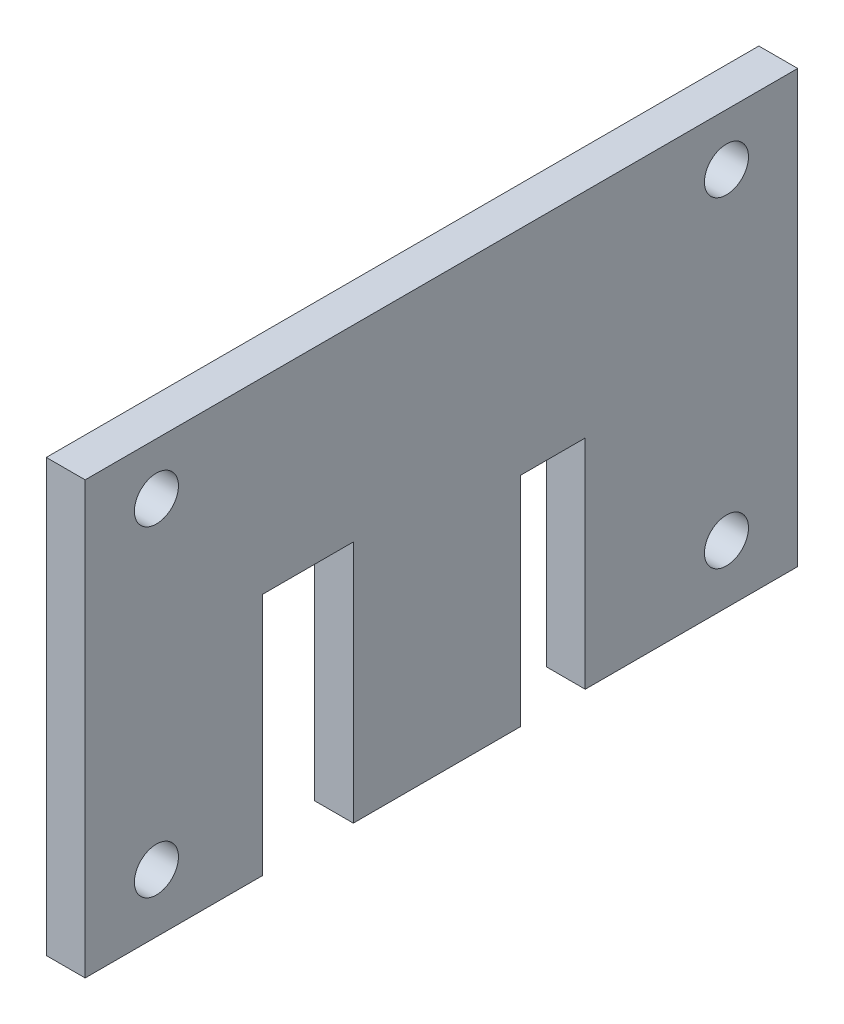
SolidWorks part; units mm, degrees
ref_plane "Front Plane" through (0, 0, 0) normal (0, 0, 1) x (1, 0, 0)
ref_plane "Top Plane" through (0, 0, 0) normal (0, 1, 0) x (1, 0, 0)
ref_plane "Right Plane" through (0, 0, 0) normal (1, 0, 0) x (0, 0, -1)
ref_plane "PX72_4" through (72.4, 0, 0) normal (1, 0, 0) x (0, 0, -1)
sketch "Sketch1" plane through (72.4, 0, 0) normal (1, 0, 0) x (0, 0, -1)
  line L0 (-99.5, -26.8) -> (-44.5, -26.8)
  line L1 (-44.5, -26.8) -> (-44.5, 6.5)
  line L2 (-44.5, 6.5) -> (-99.5, 6.5)
  line L3 (-99.5, 6.5) -> (-99.5, -26.8)
extrude "Cover Plate" add sketch "Sketch1" along normal blind 3
ref_plane "PX71_4" through (71.4, 0, 0) normal (1, 0, 0) x (0, 0, -1)
sketch "Sketch2" plane through (71.4, 0, 0) normal (1, 0, 0) x (0, 0, -1)
  line L0 (-85.8, -27.8) -> (-78.8, -27.8)
  line L1 (-78.8, -27.8) -> (-78.8, -8)
  line L2 (-78.8, -8) -> (-85.8, -8)
  line L3 (-85.8, -8) -> (-85.8, -27.8)
  line L4 (-65.9, -27.8) -> (-60.9, -27.8)
  line L5 (-60.9, -27.8) -> (-60.9, -10)
  line L6 (-60.9, -10) -> (-65.9, -10)
  line L7 (-65.9, -10) -> (-65.9, -27.8)
extrude "Cable Notches" cut sketch "Sketch2" along normal blind 5
sketch "Sketch3" plane through (71.4, 0, 0) normal (1, 0, 0) x (0, 0, -1)
  circle A0 centre (-94, -22.3) radius 1.7
  circle A1 centre (-94, 2.5) radius 1.7
  circle A2 centre (-50, -22.3) radius 1.7
  circle A3 centre (-50, 2.5) radius 1.7
extrude "Screw Holes" cut sketch "Sketch3" along normal blind 5
equation "\"BOARD_REAR\" = 86.0"
equation "\"BOARD_FRONT\" = 41.0"
equation "\"BOARD_END\" = 22.0"
equation "\"BOARD_ANGLED\" = 30.0"
equation "\"BOARD_DEPTH\" = 41.8431"
equation "\"PCB_T\" = 1.6"
equation "\"ABOVE_PCB\" = 14.0"
equation "\"BELOW_PCB\" = 6.0"
equation "\"MID_PARTS_H\" = 9.0"
equation "\"BOARD_HOLE_PILOT\" = 1.6"
equation "\"J2_X\" = 19.0"
equation "\"DUPONT_DROP\" = 14.0"
equation "\"BEND_R\" = 5.0"
equation "\"BOARD_GAP\" = 3.0"
equation "\"TOF_FOV\" = 25.0"
equation "\"TOF_MARGIN_DEG\" = 5.0"
equation "\"TOF_WIN_MARGIN\" = 1.0"
equation "\"TOF_Z\" = 9.0"
equation "\"TOF_SIDE_BEARING\" = 90.0"
equation "\"TOF_CONE_LEN\" = 70.0"
equation "\"CAM_W\" = 29.2"
equation "\"CAM_H\" = 28.2"
equation "\"CAM_D\" = 12.35"
equation "\"CAM_FRONT_Y\" = 43.0"
equation "\"CAM_BOTTOM_Z\" = 17.0"
equation "\"CAM_LENS_UP\" = 11.6"
equation "\"CAM_LENS_OPEN\" = 9.6"
equation "\"CAM_HFOV\" = 53.5"
equation "\"CAM_VFOV\" = 41.41"
equation "\"CAM_FOV_MARGIN\" = 3.0"
equation "\"CAM_FIT\" = 0.3"
equation "\"RIBBON_W\" = 16.0"
equation "\"RIBBON_T\" = 0.3"
equation "\"RIBBON_LEN\" = 150.0"
equation "\"RIBBON_EXIT_Y\" = 35.0"
equation "\"WALL\" = 2.4"
equation "\"HEAD_X\" = 48.4"
equation "\"HEAD_REAR_Y\" = -11.9"
equation "\"CAM_FOAM\" = 2.8"
equation "\"HEAD_FRONT_Y\" = 48.2"
equation "\"HEAD_TOP_Z\" = 50.6"
equation "\"HEAD_BOT_Z\" = -28.4"
equation "\"HEAD_SPLIT_Z\" = -4.0"
equation "\"SKIRT_T\" = 1.2"
equation "\"SKIRT_H\" = 3.0"
equation "\"SKIRT_FIT\" = 0.3"
equation "\"VISOR\" = 7.8"
equation "\"VISOR_Z\" = 40.0"
equation "\"ROOF_SLOPE_Y\" = 40.0"
equation "\"ROOF_CHAMFER\" = 10.0"
equation "\"REAR_CHAMFER\" = 10.0"
equation "\"CORNER_CHAMFER\" = 6.0"
equation "\"LOWER_SIDE_FACET\" = 6.0"
equation "\"LIGHTBAR_DEPTH\" = 1.0"
equation "\"HOOD_Z\" = 14.0"
equation "\"HOOD_L\" = 6.0"
equation "\"SIDE_HOOD_L\" = 4.0"
equation "\"INSERT_M3_D\" = 4.0"
equation "\"INSERT_M3_L\" = 6.0"
equation "\"M3_CLEAR\" = 3.4"
equation "\"M2_PILOT\" = 1.6"
equation "\"M25_PILOT\" = 2.2"
equation "\"BOX_X\" = 72.4"
equation "\"BOX_FRONT_Y\" = -11.9"
equation "\"BOX_REAR_Y\" = -124.4"
equation "\"BOX_BOT_Z\" = -28.4"
equation "\"BOX_TOP_Z\" = 28.0"
equation "\"LID_T\" = 2.4"
equation "\"LID_SKIRT\" = 1.6"
equation "\"LID_TONGUE_H\" = 3.0"
equation "\"LID_FIT\" = 0.3"
equation "\"PI_STANDOFF\" = 10.0"
equation "\"BOX_REAR_CHAMFER\" = 8.0"
equation "\"BOX_REAR_FACET\" = 4.0"
equation "\"VENT_UPSTAND\" = 3.0"
equation "\"TUBE_D\" = 22.2"
equation "\"TUBE_LINER\" = 1.0"
equation "\"MOUNT_Y\" = -70.0"
equation "\"RAIL_W\" = 30.0"
equation "\"RAIL_W2\" = 38.0"
equation "\"RAIL_H\" = 6.0"
equation "\"SLIDE\" = 0.3"
equation "\"STOP_T\" = 6.0"
equation "\"CLAMP_W\" = 40.0"
equation "\"CLAMP_HALF\" = 20.0"
equation "\"CLAMP_DROP\" = 12.0"
equation "\"CAP_T\" = 12.0"
equation "\"CLAMP_BOLT_OFF\" = 16.6"
equation "\"M5_INSERT_D\" = 6.4"
equation "\"M5_CLEAR\" = 5.5"
equation "\"LOCK_D\" = 3.3"
equation "\"POD_TILT_DEG\" = 0.0"
equation "\"PRINT_LIMIT\" = 180.0"
equation "\"PI5_L\" = 85.0"
equation "\"PI5_W\" = 56.0"
equation "\"PI5_T\" = 1.6"
equation "\"PI5_USBC_BX\" = 11.2"
equation "\"PI5_ETH_BY\" = 10.2"
equation "\"PI5_PORT_OVERHANG\" = 3.0"
equation "\"PI5_FPC_H\" = 5.0"
equation "\"PI5_FPC_USE\" = 0.0"
equation "\"PI5_PIN1_BX\" = 8.37"
equation "\"HEADER_BASE_H\" = 2.5"
equation "\"DUPONT_L\" = 14.0"
equation "\"PI5_UNDERSIDE\" = 1.5"
equation "\"COOLER_H\" = 15.0"
equation "\"HAT_W\" = 65.0"
equation "\"HAT_D\" = 56.5"
equation "\"HAT_T\" = 1.6"
equation "\"HAT_SPACER\" = 16.0"
equation "\"HAILO_H\" = 10.0"
equation "\"STACK_PINS_H\" = 6.0"
equation "\"DUPONT_SEAT\" = 0.5"
equation "\"PCIE_FFC_LOOP\" = 6.0"
equation "\"HAILO_AIR_GAP_MIN\" = 8.0"
equation "\"M25_CLEAR\" = 2.7"
equation "\"PI_X0\" = -55.0"
equation "\"PI_Y1\" = -36.5"
equation "\"PI_Y0\" = -92.5"
equation "\"BOX_LEN\" = 112.5"
equation "\"COVER_T\" = 3.0"
equation "\"COVER_TOP_Z\" = 6.5"
equation "\"SIDE_LEDGE_Z\" = -0.5"
equation "\"UPPER_LEDGE_Z\" = 17.0"
equation "\"REAR_LEDGE_Z\" = 8.0"
equation "\"LEDGE_L\" = 4.0"
equation "\"LEDGE_TIP\" = 1.5"
equation "\"RIBBON_W_PI\" = 11.5"
equation "\"RIBBON_RUN_Z\" = 12.0"
equation "\"RIBBON_SPEC_LEN\" = 200.0"
